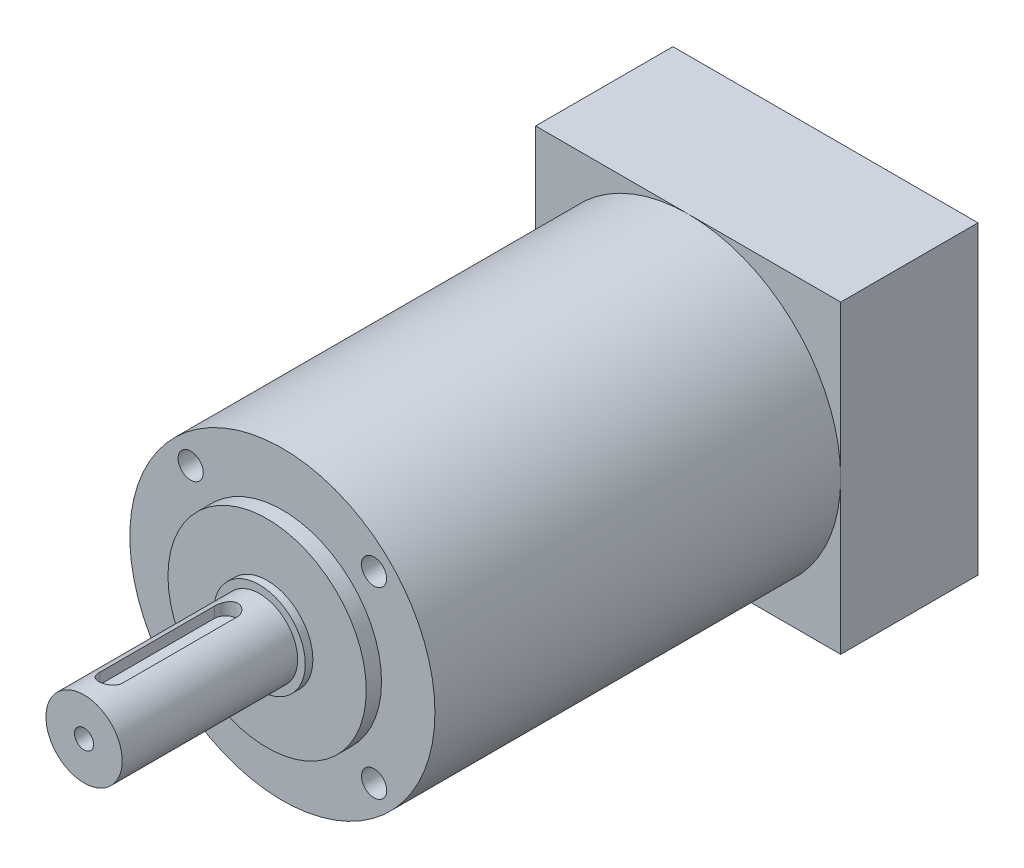
SolidWorks part; units mm, degrees
ref_plane "Front" through (0, 0, 0) normal (0, 0, 1) x (1, 0, 0)
ref_plane "Top" through (0, 0, 0) normal (0, 1, 0) x (1, 0, 0)
ref_plane "Right" through (0, 0, 0) normal (1, 0, 0) x (0, 0, -1)
sketch "Эскиз1" plane through (0, 0, 0) normal (0, 0, 1) x (1, 0, 0)
  line L1 (0, 0) -> (40, 0)
  line L2 (0, 0) -> (0, 40)
  line L3 (0, 40) -> (40, 40)
  line L4 (40, 0) -> (40, 40)
  dimension "D1" = 40
  dimension "D2" = 40
extrude "Бобышка-Вытянуть1" add sketch "Эскиз1" along normal blind 18
sketch "Эскиз2" plane through (0, 0, 18) normal (0, 0, 1) x (1, 0, 0)
  line L1 (0, 0) -> (40, 0) construction
  line L2 (40, 0) -> (40, 40) construction
  circle A0 centre (20, 20) radius 20
  dimension "D1" = 40
extrude "Бобышка-Вытянуть2" add sketch "Эскиз2" along normal blind 53.2
sketch "Эскиз3" plane through (0, 0, 71.2) normal (0, 0, 1) x (1, 0, 0)
  circle A0 centre (20, 20) radius 13
  arc A1 (40, 20) -> (20, 40) centre (20, 20) ccw construction
  dimension "D1" = 26
extrude "Бобышка-Вытянуть3" add sketch "Эскиз3" along normal blind 2
sketch "Эскиз4" plane through (0, 0, 73.2) normal (0, 0, 1) x (1, 0, 0)
  circle A0 centre (20, 20) radius 6
  circle A1 centre (20, 20) radius 13 construction
  dimension "D1" = 12
extrude "Бобышка-Вытянуть4" add sketch "Эскиз4" along normal blind 1
sketch "Эскиз5" plane through (0, 0, 74.2) normal (0, 0, 1) x (1, 0, 0)
  circle A0 centre (20, 20) radius 5
  circle A1 centre (20, 20) radius 6 construction
  dimension "D1" = 10
extrude "Бобышка-Вытянуть5" add sketch "Эскиз5" along normal blind 23 contours A0
ref_plane "Плоскость3" through (0, 25, 0) normal (0, -1, 0) x (-1, 0, 0)
sketch "Эскиз9" plane through (0, 25, 0) normal (0, -1, 0) x (-1, 0, 0)
  line L0 (-19.5685, -93.2) -> (-19.5685, -78.2) construction
  line L1 (-21.0685, -93.2) -> (-21.0685, -78.2)
  line L2 (-18.0685, -93.2) -> (-18.0685, -78.2)
  line L3 (-25, -97.2) -> (-15, -97.2) construction
  arc A0 (-21.0685, -93.2) -> (-18.0685, -93.2) centre (-19.5685, -93.2) ccw
  arc A1 (-18.0685, -78.2) -> (-21.0685, -78.2) centre (-19.5685, -78.2) ccw
  point P2 (-19.5685, -85.7)
  dimension "D2" = 1.5
  dimension "D1" = 15
  dimension "D3" = 4
extrude "Вырез-Вытянуть1" cut sketch "Эскиз9" along normal blind 1.8
hole_wizard "Отверстие обработанное метчиком M31" positions "Эскиз11" profile "Эскиз10" tap size "M3" standard "DIN"
sketch "Эскиз11" plane through (0, 0, 97.2) normal (0, 0, 1) x (1, 0, 0)
  circle A0 centre (20, 20) radius 6 construction
  point P0 (20, 20)
sketch "Эскиз10" plane through (20, 20, 97.2) normal (1, 0, 0) x (0, -1, 0)
  line L0 (0, 0) -> (0, 15.7511)
  line L1 (0, 15.7511) -> (1.25, 15)
  line L2 (1.25, 15) -> (1.25, 0)
  line L5 (1.25, 0) -> (0, 0)
  line L10 (0, 15.7511) -> (-1.25, 15) construction
  line L11 (0, -6.35) -> (0, 107.95) construction
  dimension "Диаметр сверла" = 2.5
  dimension "Глубина сверла" = 15
  dimension "Угол заточки сверла" = 118
cosmetic thread "Отверстие резьбы1" parameters "D1"=10, "D2"=3
sketch "Эскиз12" plane through (0, 0, 71.2) normal (0, 0, 1) x (1, 0, 0)
  line L0 (7.9792, 32.0208) -> (20, 20)
  line L1 (20, 20) -> (3, 20)
  circle A0 centre (20, 20) radius 17
  point P3 (7.9792, 32.0208)
  dimension "D1" = 34
  dimension "D2" = 45
hole_wizard "Отверстие обработанное метчиком M41" positions "Эскиз13" profile "Эскиз14" tap size "M4" standard "DIN"
sketch "Эскиз13" plane through (0, 0, 71.2) normal (0, 0, 1) x (1, 0, 0)
  point P0 (7.9792, 32.0208)
sketch "Эскиз14" plane through (7.9792, 32.0208, 71.2) normal (1, 0, 0) x (0, -1, 0)
  line L0 (0, 0) -> (0, 7.9914)
  line L1 (0, 7.9914) -> (1.65, 7)
  line L2 (1.65, 7) -> (1.65, 0)
  line L5 (1.65, 0) -> (0, 0)
  line L10 (0, 7.9914) -> (-1.65, 7) construction
  line L11 (0, -6.35) -> (0, 107.95) construction
  dimension "Диаметр сверла" = 3.3
  dimension "Глубина сверла" = 7
  dimension "Угол заточки сверла" = 118
cosmetic thread "Отверстие резьбы2" parameters "D1"=7, "D2"=4
pattern_circular "Круговой массив1" count 4 over 360 about axis through (20, 20, 71.2) along (0, 0, 1) of "Отверстие обработанное метчиком M41"
cosmetic thread "Отверстие резьбы3" parameters "D1"=7, "D2"=4
cosmetic thread "Отверстие резьбы4" parameters "D1"=7, "D2"=4
cosmetic thread "Отверстие резьбы5" parameters "D1"=7, "D2"=4
